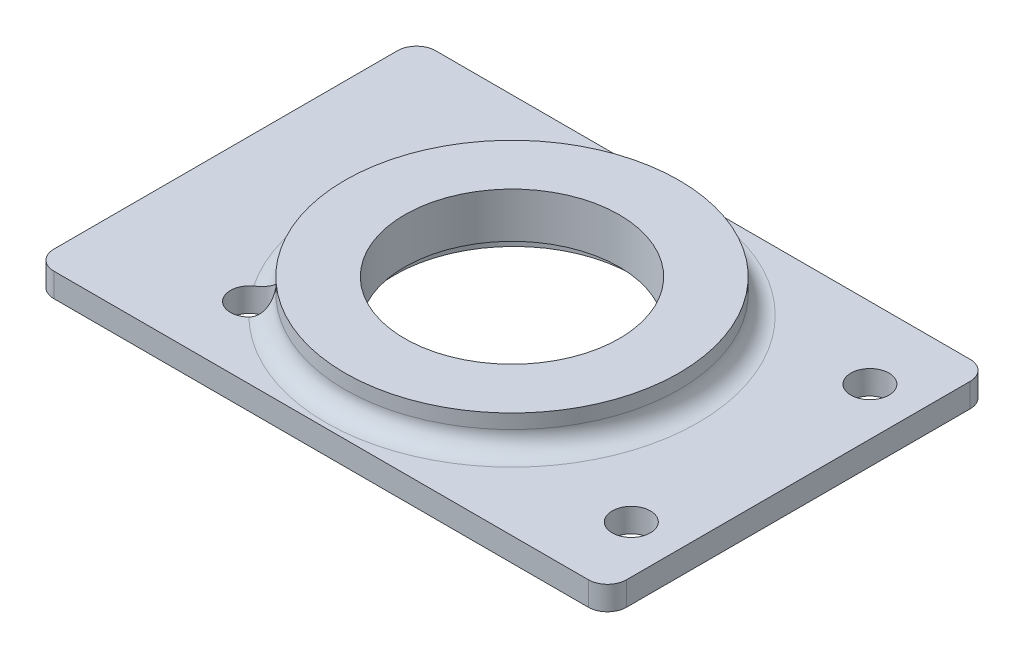
SolidWorks part; units mm, degrees
ref_plane "Front Plane" through (0, 0, 0) normal (0, 0, 1) x (1, 0, 0)
ref_plane "Top Plane" through (0, 0, 0) normal (0, 1, 0) x (1, 0, 0)
ref_plane "Right Plane" through (0, 0, 0) normal (1, 0, 0) x (0, 0, -1)
sketch "Sketch1" plane through (0, 0, 0) normal (0, 1, 0) x (1, 0, 0)
  line L1 (0, 0) -> (76.2, 0)
  line L2 (0, 0) -> (0, 50.8)
  line L3 (0, 50.8) -> (76.2, 50.8)
  line L4 (76.2, 0) -> (76.2, 50.8)
  circle A0 centre (38.1, 25.4) radius 14.2748
  dimension "D5" = 28.5496
  dimension "D1" = 50.8
  dimension "D2" = 76.2
  dimension "D3" = 38.1
  dimension "D4" = 25.4
extrude "Boss-Extrude1" add sketch "Sketch1" along normal blind 3.175
sketch "Sketch2" plane through (0, 3.175, 0) normal (0, 1, 0) x (1, 0, 0)
  circle A0 centre (38.1, 25.4) radius 22.225
  dimension "D1" = 44.45
extrude "Boss-Extrude2" add sketch "Sketch2" along normal blind 4.445
sketch "Sketch3" plane through (0, 3.175, 0) normal (0, -1, 0) x (1, 0, 0)
  circle A1 centre (38.1, -25.4) radius 14.2748
  circle A2 centre (38.1, -25.4) radius 14.2748
  dimension "D1" = 0
extrude "Cut-Extrude1" cut sketch "Sketch3" against normal through all
sketch "Sketch4" plane through (0, 0, 0) normal (0, -1, 0) x (-1, 0, 0)
  line L0 (0, 0) -> (-76.2, 0) construction
  circle A0 centre (-38.3325, 25.4) radius 15.8623
  dimension "D1" = 31.7246
  dimension "D2" = 25.4
extrude "Cut-Extrude2" cut sketch "Sketch4" against normal blind 1.6002
fillet "Fillet1" radius 2.54 1 edges at (38.1, 3.175, -47.625)
fillet "Fillet2" radius 2.54 4 edges at (0, 1.5875, -50.8) (76.2, 1.5875, -50.8) (0, 1.5875, 0) (76.2, 1.5875, 0)
sketch "Sketch5" plane through (0, 3.175, 0) normal (0, 1, 0) x (1, 0, 0)
  line L0 (73.66, 50.8) -> (2.54, 50.8) construction
  line L2 (2.54, 0) -> (73.66, 0) construction
  line L3 (76.2, 2.54) -> (76.2, 48.26) construction
  circle A0 centre (69.85, 41.275) radius 2.54
  circle A1 centre (69.85, 9.525) radius 2.54
  circle A2 centre (19.05, 9.525) radius 2.54
  circle A3 centre (19.05, 41.275) radius 2.54
  point P10 (0, 0)
  point P11 (0, 0)
  dimension "D9" = 5.08
  dimension "D10" = 5.08
  dimension "D11" = 5.08
  dimension "D12" = 5.08
  dimension "D1" = 9.525
  dimension "D2" = 50.8
  dimension "D3" = 50.8
  dimension "D4" = 9.525
  dimension "D5" = 9.525
  dimension "D6" = 6.35
  dimension "D7" = 9.525
  dimension "D8" = 6.35
extrude "Cut-Extrude3" cut sketch "Sketch5" against normal through all and the other way through all
